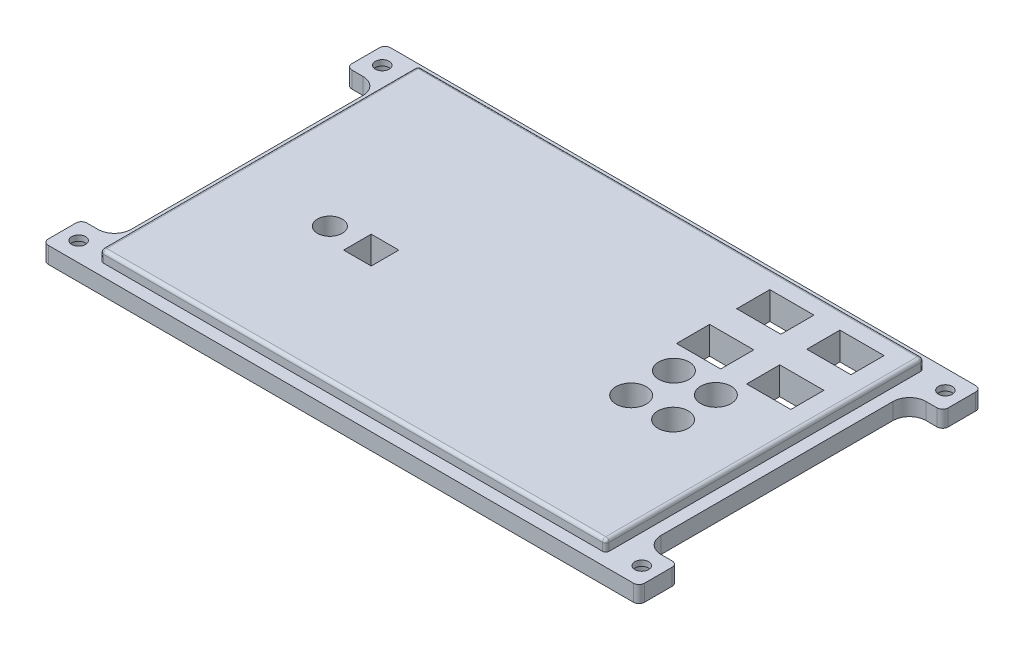
SolidWorks part; units mm, degrees
ref_plane "Спереди" through (0, 0, 0) normal (0, 0, 1) x (1, 0, 0)
ref_plane "Сверху" through (0, 0, 0) normal (0, 1, 0) x (1, 0, 0)
ref_plane "Справа" through (0, 0, 0) normal (1, 0, 0) x (0, 0, -1)
sketch "Эскиз1" plane through (0, 0, 0) normal (0, 1, 0) x (1, 0, 0)
  line L1 (-48, -31) -> (48, -31)
  line L2 (-48, -31) -> (-48, 31)
  line L3 (-48, 31) -> (48, 31)
  line L4 (48, -31) -> (48, 31)
  line L5 (-48, -31) -> (48, 31) construction
  line L6 (-48, 31) -> (48, -31) construction
  point P0 (0, 0)
  dimension "D1" = 96
  dimension "D2" = 62
extrude "Бобышка-Вытянуть1" add sketch "Эскиз1" along normal blind 5
sketch "Эскиз2" plane through (0, 5, 0) normal (0, 1, 0) x (1, 0, 0)
  line L0 (48, 31) -> (-48, 31) construction
  line L1 (-45.8, -28.8) -> (45.8, -28.8)
  line L2 (-45.8, -28.8) -> (-45.8, 28.8)
  line L3 (-45.8, 28.8) -> (45.8, 28.8)
  line L4 (45.8, -28.8) -> (45.8, 28.8)
  line L5 (-45.8, -28.8) -> (45.8, 28.8) construction
  line L6 (-45.8, 28.8) -> (45.8, -28.8) construction
  line L7 (48, -31) -> (48, 31) construction
  line L12 (48, -31) -> (48, 31)
  line L13 (48, 31) -> (-48, 31)
  line L14 (-48, 31) -> (-48, -31)
  line L15 (-48, -31) -> (48, -31)
  line L16 (48, -31) -> (48, 31)
  line L17 (48, 31) -> (-48, 31)
  line L18 (-48, 31) -> (-48, -31)
  line L19 (-48, -31) -> (48, -31)
  point P0 (0, 0)
  dimension "D1" = 2.2
  dimension "D2" = 2.2
  dimension "D3" = 0
extrude "Вырез-Вытянуть1" cut sketch "Эскиз2" against normal blind 2
sketch "Эскиз4" plane through (0, 0, 0) normal (0, -1, 0) x (1, 0, 0)
  line L1 (-54, -31) -> (54, -31)
  line L2 (-54, -31) -> (-54, 31)
  line L3 (-54, 31) -> (54, 31)
  line L4 (54, -31) -> (54, 31)
  line L5 (-54, -31) -> (54, 31) construction
  line L6 (-54, 31) -> (54, -31) construction
  line L7 (51, -27.5) -> (-51, -27.5)
  line L8 (51, -27.5) -> (51, 27.5)
  line L9 (51, 27.5) -> (-51, 27.5)
  line L10 (-51, -27.5) -> (-51, 27.5)
  line L11 (51, -27.5) -> (-51, 27.5) construction
  line L12 (51, 27.5) -> (-51, -27.5) construction
  line L13 (-54, -24) -> (54, -24)
  line L14 (-54, -24) -> (-54, 24)
  line L15 (-54, 24) -> (54, 24)
  line L16 (54, -24) -> (54, 24)
  line L17 (-54, -24) -> (54, 24) construction
  line L18 (-54, 24) -> (54, -24) construction
  circle A0 centre (51, 27.5) radius 1.25
  circle A1 centre (51, -27.5) radius 1.25
  circle A2 centre (-51, -27.5) radius 1.25
  circle A3 centre (-51, 27.5) radius 1.25
  point P0 (0, 0)
  point P6 (0, 0)
  point P15 (0, 0)
  line M15 (48, -31) -> (48, 31)
  line M17 (-48, 31) -> (-48, -31)
  dimension "D5" = 2.5
  dimension "D1" = 108
  dimension "D2" = 62
  dimension "D3" = 55
  dimension "D4" = 102
  dimension "D6" = 7
extrude "Бобышка-Вытянуть2" add sketch "Эскиз4" against normal blind 3 contours A3 L9 L3 L2 L15 L10 M17 | A3 L10 L15 L9 M17 | A2 L10 L13 L2 L1 L7 M17 | A2 L7 L13 L10 M17 | A1 L7 L1 L4 L13 L8 M15 | A1 L8 L13 L7 M15 | A0 L8 L15 L4 L3 L9 M15 | A0 L9 L15 L8 M15 region at (-53.9078, 0, -27.5) region at (48.0922, 0, -29.25) region at (-49.3717, 0, -25.5886) region at (-53.9078, 0, 27.5) region at (49.3717, 0, -25.5886) region at (-49.3717, 0, 25.5886) region at (52.5, 0, 24.0922) region at (49.3717, 0, 25.5886)
fillet "Скругление1" radius 3 4 edges at (-48, 1.5, -24) (-48, 1.5, 24) (48, 1.5, -24) (48, 1.5, 24)
fillet "Скругление2" radius 1 8 edges at (-54, 1.5, 24) (-54, 1.5, 31) (-54, 1.5, -24) (-54, 1.5, -31) (54, 1.5, -31) (54, 1.5, -24) (54, 1.5, 31) (54, 1.5, 24)
fillet "Скругление3" radius 0.6 4 edges at (0, 5, 28.8) (-45.8, 5, 0) (0, 5, -28.8) (45.8, 5, 0)
fillet "Скругление4" radius 0.6 8 edges at (-45.6243, 4.8243, -28.6243) (45.6243, 4.8243, -28.6243) (45.6243, 4.8243, 28.6243) (-45.6243, 4.8243, 28.6243) (-45.8, 3.7, -28.8) (45.8, 3.7, -28.8) (45.8, 3.7, 28.8) (-45.8, 3.7, 28.8)
sketch "Эскиз5" plane through (0, 0, 0) normal (0, -1, 0) x (1, 0, 0)
  circle A0 centre (-51, 27.5) radius 2.25
  circle A1 centre (51, 27.5) radius 2.25
  circle A2 centre (-51, -27.5) radius 2.25
  circle A3 centre (51, -27.5) radius 2.25
  dimension "D1" = 4.5
extrude "Вырез-Вытянуть2" cut sketch "Эскиз5" against normal blind 2
sketch "Эскиз6" plane through (0, 0, 0) normal (0, -1, 0) x (1, 0, 0)
  line L0 (-28.5, 4.5) -> (-21, 4.5) construction
  line L1 (-45, -27.5) -> (45, -27.5)
  line L2 (-45, -27.5) -> (-45, 27.5)
  line L3 (-45, 27.5) -> (45, 27.5)
  line L4 (45, -27.5) -> (45, 27.5)
  line L5 (-45, -27.5) -> (45, 27.5) construction
  line L6 (-45, 27.5) -> (45, -27.5) construction
  line L7 (34, -8.5) -> (42, -8.5)
  line L8 (-23.5, 2) -> (-18.5, 2)
  line L9 (-23.5, 2) -> (-23.5, 7)
  line L10 (-23.5, 7) -> (-18.5, 7)
  line L11 (-18.5, 2) -> (-18.5, 7)
  line L12 (-23.5, 2) -> (-18.5, 7) construction
  line L13 (-23.5, 7) -> (-18.5, 2) construction
  line L14 (21.3, -8.5) -> (29.3, -8.5)
  line L15 (21.3, -8.5) -> (21.3, -14.5)
  line L16 (21.3, -14.5) -> (29.3, -14.5)
  line L17 (29.3, -8.5) -> (29.3, -14.5)
  line L18 (21.3, -8.5) -> (29.3, -14.5) construction
  line L19 (21.3, -14.5) -> (29.3, -8.5) construction
  line L20 (34, -8.5) -> (34, -14.5)
  line L21 (34, -14.5) -> (42, -14.5)
  line L22 (42, -8.5) -> (42, -14.5)
  line L23 (34, -8.5) -> (42, -14.5) construction
  line L24 (34, -14.5) -> (42, -8.5) construction
  line L25 (34, -19.4) -> (42, -19.4)
  line L26 (34, -19.4) -> (34, -25.4)
  line L27 (34, -25.4) -> (42, -25.4)
  line L28 (42, -19.4) -> (42, -25.4)
  line L29 (34, -19.4) -> (42, -25.4) construction
  line L30 (34, -25.4) -> (42, -19.4) construction
  line L31 (21.3, -19.4) -> (29.3, -19.4)
  line L32 (21.3, -19.4) -> (21.3, -25.4)
  line L33 (21.3, -25.4) -> (29.3, -25.4)
  line L34 (29.3, -19.4) -> (29.3, -25.4)
  line L35 (21.3, -19.4) -> (29.3, -25.4) construction
  line L36 (21.3, -25.4) -> (29.3, -19.4) construction
  circle A0 centre (-28.5, 4.5) radius 2.25
  circle A1 centre (25.33, 3.75) radius 2.75
  circle A2 centre (32.93, 3.75) radius 2.75
  circle A3 centre (32.93, -4) radius 2.75
  circle A4 centre (25.33, -4) radius 2.75
  point P0 (0, 0)
  point P24 (25.3, -11.5)
  point P29 (38, -11.5)
  point P34 (38, -22.4)
  point P39 (25.3, -22.4)
  dimension "D5" = 4.5
  dimension "D8" = 5.5
  dimension "D1" = 90
  dimension "D2" = 55
  dimension "D3" = 16.5
  dimension "D4" = 23
  dimension "D6" = 24
  dimension "D7" = 5
  dimension "D11" = 12.07
  dimension "D12" = 23.5
  dimension "D13" = 7.75
  dimension "D14" = 7.6
  dimension "D15" = 8
  dimension "D16" = 6
  dimension "D19" = 12.7
  dimension "D20" = 10.9
  dimension "D21" = 5.1
  dimension "D22" = 7
  dimension "D9" = 2
  dimension "D10" = 2
  dimension "D17" = 2
  dimension "D18" = 2
extrude "Вырез-Вытянуть3" cut sketch "Эскиз6" along direction (0, -1, 0) on the side against the normal through all contours A0 | L8 L11 L10 L9 | A4 | A3 | A2 | A1 | L17 L14 L15 L16 | L34 L31 L32 L33 | L28 L25 L26 L27 | L22 L7 L20 L21 region at (38, 0, -11.5) region at (-21, 0, 4.5) region at (25.3, 0, -11.5) region at (38, 0, -22.4) region at (25.3, 0, -22.4) region at (-28.5, 0, 4.5) region at (25.33, 0, 3.75) region at (32.93, 0, 3.75) region at (32.93, 0, -4) region at (25.33, 0, -4)
